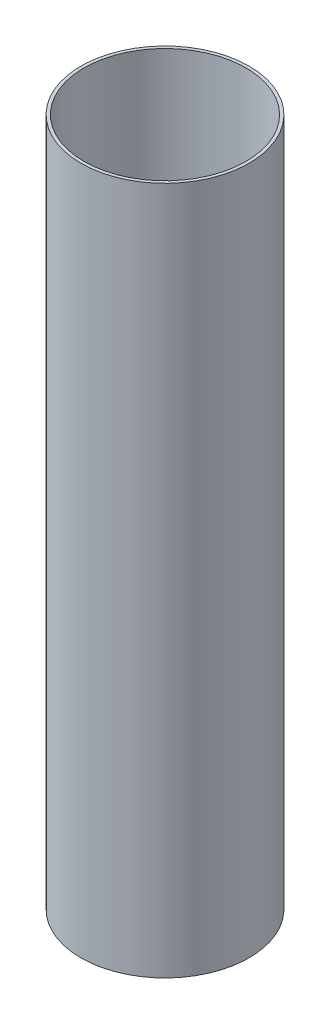
SolidWorks part; units mm, degrees
ref_plane "Front Plane" through (0, 0, 0) normal (0, 0, 1) x (1, 0, 0)
ref_plane "Top Plane" through (0, 0, 0) normal (0, 1, 0) x (1, 0, 0)
ref_plane "Right Plane" through (0, 0, 0) normal (1, 0, 0) x (0, 0, -1)
sketch "Sketch1" plane through (0, 0, 0) normal (0, 1, 0) x (1, 0, 0)
  circle A0 centre (0, 0) radius 53
  circle A1 centre (0, 0) radius 55
  dimension "D1" = 106
  dimension "D2" = 2
extrude "Boss-Extrude1" add sketch "Sketch1" along normal blind 450
